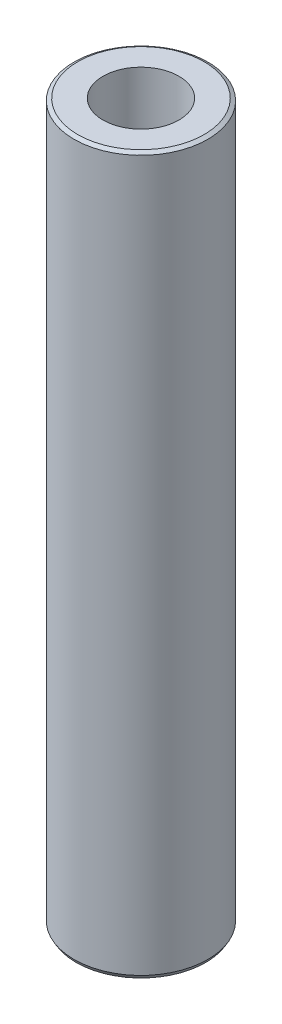
SolidWorks part; units mm, degrees
ref_plane "Front Plane" through (0, 0, 0) normal (0, 0, 1) x (1, 0, 0)
ref_plane "Top Plane" through (0, 0, 0) normal (0, 1, 0) x (1, 0, 0)
ref_plane "Right Plane" through (0, 0, 0) normal (1, 0, 0) x (0, 0, -1)
sketch "Sketch1" plane through (0, 0, 0) normal (0, 1, 0) x (1, 0, 0)
  circle A0 centre (0, 0) radius 35
  dimension "SHAFT_OD" = 70
extrude "Boss-Extrude1" add sketch "Sketch1" along normal blind 374.4501
sketch "Sketch2" plane through (0, 0, 0) normal (0, 1, 0) x (1, 0, 0)
  circle A0 centre (0, 0) radius 19.8576
  dimension "BORE_D" = 39.7151
extrude "Cut-Extrude1" cut sketch "Sketch2" along normal through all
chamfer "Chamfer1" distance 1.1399 angle 60 2 edges at (0, 374.4501, 35) (0, 0, 35) first distance on face at (0, 374.4501, 35) first distance on face at (0, 0, 19.8576)
